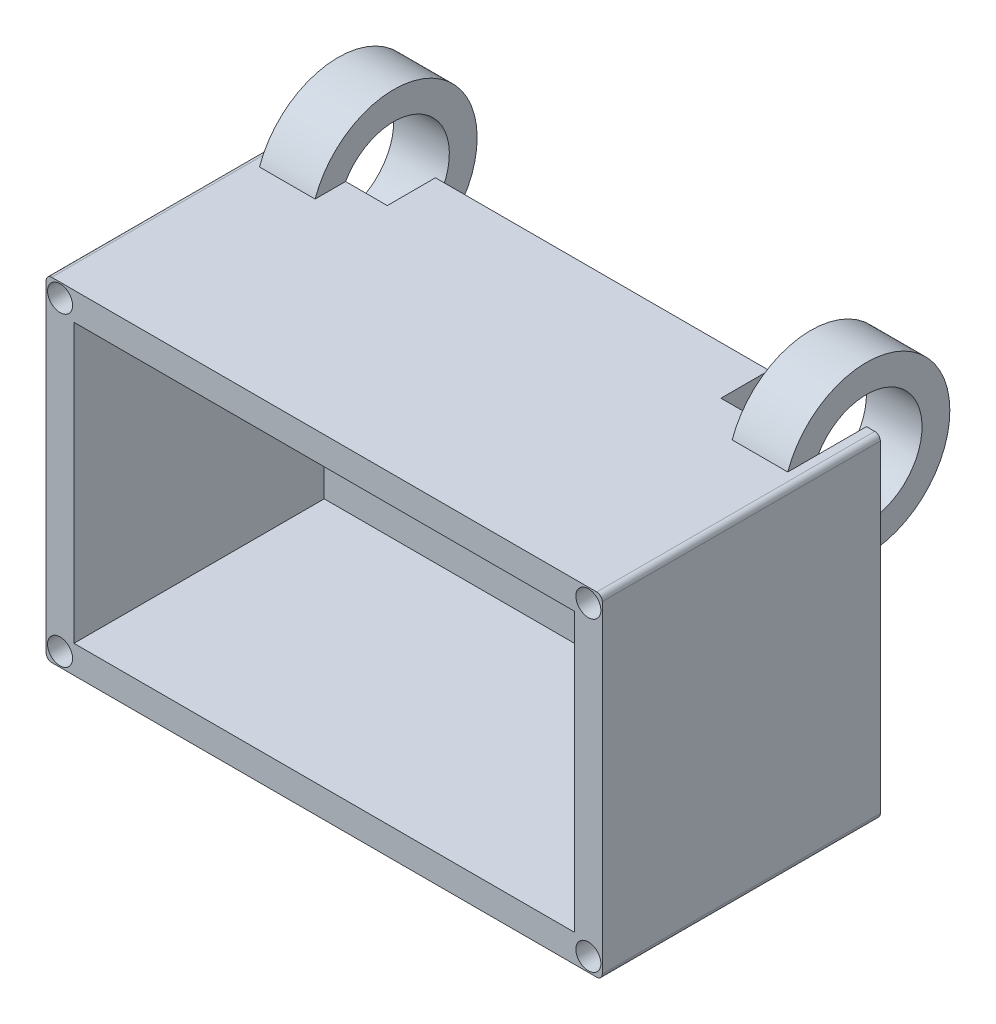
SolidWorks part; units mm, degrees
ref_plane "前视基准面" through (0, 0, 0) normal (0, 0, 1) x (1, 0, 0)
ref_plane "上视基准面" through (0, 0, 0) normal (0, 1, 0) x (1, 0, 0)
ref_plane "右视基准面" through (0, 0, 0) normal (1, 0, 0) x (0, 0, -1)
other "Configuration Table"
sketch "Sketch1" plane through (0, 0, 0) normal (0, 0, 1) x (1, 0, 0)
  line L1 (-100, -60) -> (100, -60)
  line L2 (-100, -60) -> (-100, 60)
  line L3 (-100, 60) -> (100, 60)
  line L4 (100, -60) -> (100, 60)
  line L5 (-100, -60) -> (100, 60) construction
  line L6 (-100, 60) -> (100, -60) construction
  point P0 (0, 0)
extrude "Boss-Extrude1" add sketch "Sketch1" along normal blind 100
shell "Shell1" thickness 10 removed face at (0, 0, 100)
ref_plane "Plane1" through (-75, 0, 0) normal (1, 0, 0) x (0, 0, -1)
ref_plane "Plane2" through (75, 0, 0) normal (1, 0, 0) x (0, 0, -1)
sketch "Sketch2" plane through (-75, 0, 0) normal (1, 0, 0) x (0, 0, -1)
  line L0 (0, -60) -> (0, 60) construction
  circle A0 centre (0, 50) radius 30
extrude "Boss-Extrude2" add sketch "Sketch2" against normal blind 20
sketch "Sketch3" plane through (75, 0, 0) normal (1, 0, 0) x (0, 0, -1)
  line L0 (0, -60) -> (0, 60) construction
  circle A0 centre (0, 50) radius 30
extrude "Boss-Extrude3" add sketch "Sketch3" along normal blind 20
ref_plane "Plane3" through (-95, 0, 0) normal (1, 0, 0) x (0, 0, -1)
ref_plane "Plane4" through (95, 0, 0) normal (1, 0, 0) x (0, 0, -1)
sketch "Sketch4" plane through (-95, 0, 0) normal (1, 0, 0) x (0, 0, -1)
  line L0 (0, -60) -> (0, 60) construction
  circle A0 centre (0, 50) radius 20
extrude "Cut-Extrude1" cut sketch "Sketch4" along normal blind 35
sketch "Sketch5" plane through (95, 0, 0) normal (1, 0, 0) x (0, 0, -1)
  line L0 (0, -60) -> (0, 60) construction
  circle A0 centre (0, 50) radius 20
extrude "Cut-Extrude2" cut sketch "Sketch5" against normal blind 35
ref_plane "Plane5" through (0, 0, 100) normal (0, 0, 1) x (1, 0, 0)
sketch "Sketch7" plane through (0, 0, 100) normal (0, 0, 1) x (1, 0, 0)
  line L0 (95, -71.5) -> (95, 71.5) construction
  line L1 (-95, -71.5) -> (-95, 71.5) construction
  circle A0 centre (95, 55) radius 4.5
  circle A1 centre (95, -55) radius 4.5
  circle A2 centre (-95, 55) radius 4.5
  circle A3 centre (-95, -55) radius 4.5
extrude "Cut-Extrude3" cut sketch "Sketch7" against normal blind 10
sketch "Sketch8" plane through (0, 0, 0) normal (0, 0, 1) x (1, 0, 0)
  line L0 (95, -71.5) -> (95, 71.5) construction
  line L1 (-95, -71.5) -> (-95, 71.5) construction
  circle A0 centre (95, 55) radius 4.5
  circle A1 centre (95, -55) radius 4.5
  circle A2 centre (-95, 55) radius 4.5
  circle A3 centre (-95, -55) radius 4.5
extrude "Cut-Extrude4" cut sketch "Sketch8" along normal blind 10
fillet "Fillet1" radius 2 4 edges at (-100, -60, 50) (-100, 60, 50) (100, -60, 50) (100, 60, 50)
ref_plane "Top_Mounting_Face" through (0, 0, 100) normal (0, 0, 1) x (1, 0, 0)
ref_plane "Bottom_Base_Face" through (0, 0, 0) normal (0, 0, 1) x (1, 0, 0)
sketch3d "3DSketch1"
  line L0 (-75, 0, 50) -> (-85, 0, 50) construction
ref_axis "Bearing_Axis_Left" through (-75, 0, 50) along (-1, 0, 0)
sketch3d "3DSketch2"
  line L0 (75, 0, 50) -> (85, 0, 50) construction
ref_axis "Bearing_Axis_Right" through (75, 0, 50) along (1, 0, 0)
